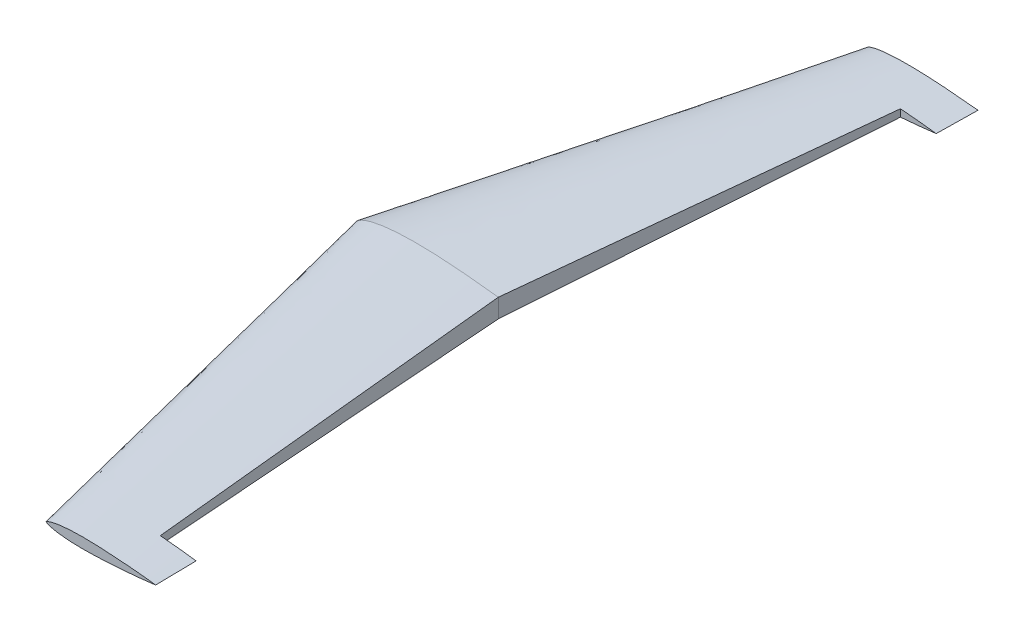
SolidWorks part; units mm, degrees
material "\"PLA\""
ref_plane "Front Plane" through (0, 0, 0) normal (0, 0, 1) x (1, 0, 0)
ref_plane "Top Plane" through (0, 0, 0) normal (0, 1, 0) x (1, 0, 0)
ref_plane "Right Plane" through (0, 0, 0) normal (1, 0, 0) x (0, 0, -1)
curve "NACA0015 top"
  spline degree 3 poles (1, 0, 0) (0.9834, 0.0035, 0) (0.9502, 0.0106, 0) (0.8834, 0.0206, 0) (0.8001, 0.0331, 0) (0.7001, 0.0461, 0) (0.6001, 0.0574, 0) (0.5001, 0.0666, 0) (0.4001, 0.0732, 0) (0.3167, 0.0755, 0) (0.25, 0.0746, 0) (0.1999, 0.0721, 0) (0.1498, 0.0673, 0) (0.108, 0.0607, 0) (0.0748, 0.0527, 0) (0.0493, 0.0448, 0) (0.0285, 0.0352, 0) (0.0083, 0.0224, 0) (0.0032, 0.0087, 0) (0, 0, 0) knots 0 0 0 0 0.049635 0.098913 0.19727 0.295402 0.393327 0.491044 0.588553 0.685896 0.734557 0.783276 0.832166 0.881486 0.906512 0.932076 0.958957 0.973952 1 1 1 1
curve "NACA0015 bottom"
  spline degree 3 poles (0, 0, 0) (0.0032, -0.0087, 0) (0.0083, -0.0224, 0) (0.0285, -0.0352, 0) (0.0493, -0.0448, 0) (0.0748, -0.0527, 0) (0.108, -0.0607, 0) (0.1498, -0.0673, 0) (0.1999, -0.0721, 0) (0.25, -0.0746, 0) (0.3167, -0.0755, 0) (0.4001, -0.0732, 0) (0.5001, -0.0666, 0) (0.6001, -0.0574, 0) (0.7001, -0.0461, 0) (0.8001, -0.0331, 0) (0.8834, -0.0206, 0) (0.9502, -0.0106, 0) (0.9834, -0.0035, 0) (1, 0, 0) knots 0 0 0 0 0.026048 0.041043 0.067924 0.093488 0.118514 0.167834 0.216724 0.265443 0.314104 0.411447 0.508956 0.606673 0.704598 0.80273 0.901087 0.950365 1 1 1 1
curve "NACA0012 top"
  spline degree 3 poles (1, 0, 0) (0.9999, 0.0005, 0) (0.9996, 0.0017, 0) (0.9971, 0.0015, 0) (0.9944, 0.0021, 0) (0.9903, 0.0026, 0) (0.9851, 0.0033, 0) (0.9787, 0.0042, 0) (0.9713, 0.0052, 0) (0.9627, 0.0064, 0) (0.9531, 0.0077, 0) (0.9424, 0.0091, 0) (0.9307, 0.0106, 0) (0.9179, 0.0122, 0) (0.9042, 0.014, 0) (0.8895, 0.0158, 0) (0.874, 0.0177, 0) (0.8575, 0.0196, 0) (0.8402, 0.0217, 0) (0.8222, 0.0237, 0) (0.8033, 0.0259, 0) (0.7838, 0.028, 0) (0.7636, 0.0302, 0) (0.7428, 0.0324, 0) (0.7214, 0.0345, 0) (0.6995, 0.0367, 0) (0.6772, 0.0388, 0) (0.6544, 0.0409, 0) (0.6313, 0.043, 0) (0.6078, 0.045, 0) (0.5841, 0.0469, 0) (0.5602, 0.0488, 0) (0.5362, 0.0505, 0) (0.5121, 0.0522, 0) (0.4879, 0.0537, 0) (0.4638, 0.0551, 0) (0.4398, 0.0563, 0) (0.4159, 0.0574, 0) (0.3922, 0.0583, 0) (0.3688, 0.0591, 0) (0.3456, 0.0596, 0) (0.3228, 0.0599, 0) (0.3005, 0.0601, 0) (0.2786, 0.06, 0) (0.2572, 0.0596, 0) (0.2364, 0.0591, 0) (0.2162, 0.0583, 0) (0.1966, 0.0572, 0) (0.1778, 0.056, 0) (0.1597, 0.0544, 0) (0.1425, 0.0527, 0) (0.126, 0.0507, 0) (0.1104, 0.0486, 0) (0.0958, 0.0462, 0) (0.0821, 0.0436, 0) (0.0693, 0.0408, 0) (0.0576, 0.0378, 0) (0.0468, 0.0347, 0) (0.0372, 0.0313, 0) (0.0286, 0.0279, 0) (0.0211, 0.0243, 0) (0.0147, 0.0206, 0) (0.0094, 0.0167, 0) (0.0053, 0.0128, 0) (0.0023, 0.0087, 0) (0.0004, 0.0044, 0) (0.0001, 0.0014, 0) (0, 0, 0) knots 0 0 0 0 0.001434 0.003166 0.006048 0.010073 0.015231 0.02151 0.028895 0.037368 0.046909 0.057494 0.069098 0.081695 0.095252 0.10974 0.125123 0.141363 0.158425 0.176266 0.194845 0.214118 0.234038 0.25456 0.275635 0.297214 0.319245 0.341677 0.364458 0.387533 0.410848 0.434349 0.457981 0.481687 0.505414 0.529104 0.552705 0.576159 0.599415 0.622418 0.645114 0.667453 0.689385 0.71086 0.731829 0.752247 0.77207 0.791254 0.809759 0.827545 0.844576 0.860818 0.876238 0.890807 0.904501 0.917294 0.929169 0.940111 0.950113 0.959173 0.967302 0.974522 0.980879 0.986449 0.991356 0.995786 1 1 1 1
sketch "Sketch3" plane through (0, 0, 0) normal (0, 0, 1) x (1, 0, 0)
  line L0 (0, 0) -> (1, 0) construction
  spline S0 degree 3 poles (0, 0) (0.0024, 0.0105) (0.0128, 0.0277) (0.0398, 0.0405) (0.0646, 0.05) (0.0904, 0.0566) (0.1157, 0.0618) (0.1436, 0.0662) (0.1764, 0.07) (0.2112, 0.0727) (0.2448, 0.0742) (0.2768, 0.075) (0.3075, 0.0751) (0.3387, 0.0747) (0.3674, 0.0739) (0.3979, 0.0727) (0.4325, 0.0709) (0.4699, 0.0685) (0.5072, 0.0656) (0.542, 0.0627) (0.5776, 0.0593) (0.6101, 0.056) (0.6429, 0.0525) (0.6719, 0.0492) (0.7011, 0.0457) (0.7283, 0.0423) (0.7621, 0.038) (0.7953, 0.0335) (0.8265, 0.029) (0.8531, 0.0251) (0.8826, 0.0207) (0.9141, 0.016) (0.9536, 0.0098) (0.9814, 0.004) (1, 0) knots 0 0 0 0 0.031271 0.055077 0.085653 0.108858 0.132715 0.161158 0.191102 0.229169 0.263044 0.289323 0.322456 0.35268 0.380449 0.406317 0.441553 0.481621 0.515849 0.550731 0.583502 0.620296 0.646048 0.679661 0.705503 0.732118 0.759389 0.805025 0.829931 0.851453 0.883388 0.917173 0.94435 1 1 1 1
  spline S5 degree 3 poles (1, 0) (0.9834, 0.0035) (0.9502, 0.0106) (0.8834, 0.0206) (0.8001, 0.0331) (0.7001, 0.0461) (0.6001, 0.0574) (0.5001, 0.0666) (0.4001, 0.0732) (0.3167, 0.0755) (0.25, 0.0746) (0.1999, 0.0721) (0.1498, 0.0673) (0.108, 0.0607) (0.0748, 0.0527) (0.0493, 0.0448) (0.0285, 0.0352) (0.0083, 0.0224) (0.0032, 0.0087) (0, 0) knots 0 0 0 0 0.049635 0.098913 0.19727 0.295402 0.393327 0.491044 0.588553 0.685896 0.734557 0.783276 0.832166 0.881486 0.906512 0.932076 0.958957 0.973952 1 1 1 1 construction
  spline S6 degree 3 poles (0, 0) (0.0026, -0.0103) (0.0124, -0.0274) (0.0352, -0.0382) (0.0549, -0.0467) (0.0763, -0.0531) (0.0989, -0.0585) (0.1215, -0.0628) (0.1441, -0.0662) (0.1678, -0.069) (0.1929, -0.0713) (0.2187, -0.073) (0.2432, -0.0741) (0.2682, -0.0748) (0.294, -0.0751) (0.3226, -0.075) (0.3496, -0.0744) (0.375, -0.0736) (0.3993, -0.0726) (0.4287, -0.0711) (0.4578, -0.0693) (0.4876, -0.0672) (0.5131, -0.0651) (0.5405, -0.0628) (0.5658, -0.0605) (0.5917, -0.0579) (0.6171, -0.0553) (0.6443, -0.0523) (0.6723, -0.0491) (0.6988, -0.046) (0.7231, -0.043) (0.7453, -0.0402) (0.768, -0.0372) (0.792, -0.0339) (0.8205, -0.0299) (0.8472, -0.026) (0.8731, -0.0221) (0.8949, -0.0189) (0.9178, -0.0154) (0.9394, -0.012) (0.9668, -0.0071) (0.9865, -0.0029) (1, 0) knots 0 0 0 0 0.031459 0.053378 0.072332 0.094059 0.118323 0.140338 0.161138 0.184859 0.210284 0.23444 0.260514 0.281647 0.30767 0.335622 0.365097 0.386713 0.409735 0.436157 0.472686 0.494853 0.5233 0.547147 0.575234 0.597407 0.623047 0.64982 0.677353 0.70536 0.727695 0.748701 0.770694 0.794596 0.819514 0.854489 0.873511 0.895859 0.918771 0.94123 0.959662 1 1 1 1
  spline S8 degree 3 poles (0, 0) (0, 0.0056) (0.0044, 0.0125) (0.012, 0.0188) (0.0216, 0.0249) (0.0334, 0.0301) (0.0509, 0.036) (0.0662, 0.0401) (0.084, 0.044) (0.0995, 0.0468) (0.1185, 0.0498) (0.1371, 0.0521) (0.1565, 0.0541) (0.1756, 0.0558) (0.1977, 0.0573) (0.2208, 0.0585) (0.2443, 0.0593) (0.2675, 0.0598) (0.2927, 0.0601) (0.3191, 0.06) (0.3457, 0.0596) (0.3715, 0.059) (0.3982, 0.0581) (0.4251, 0.057) (0.4546, 0.0556) (0.4861, 0.0538) (0.5172, 0.0519) (0.5479, 0.0497) (0.578, 0.0474) (0.6105, 0.0448) (0.6427, 0.042) (0.6728, 0.0393) (0.6998, 0.0367) (0.7284, 0.0338) (0.7575, 0.0308) (0.7894, 0.0274) (0.8221, 0.0238) (0.8573, 0.0197) (0.8931, 0.0154) (0.9405, 0.0093) (0.976, 0.0049) (1, 0) knots 0 0 0 0 0.015534 0.023148 0.028948 0.048951 0.06074 0.083424 0.095373 0.114484 0.12984 0.151868 0.169556 0.187127 0.208334 0.23486 0.255026 0.277502 0.303157 0.329099 0.355311 0.381272 0.40523 0.433818 0.460412 0.492192 0.526716 0.552057 0.582577 0.615545 0.647969 0.677813 0.704526 0.727746 0.762394 0.790552 0.82209 0.859297 0.894761 0.928143 1 1 1 1
  spline S10 degree 3 poles (0, 0) (0, -0.0056) (0.0044, -0.0125) (0.012, -0.0188) (0.0216, -0.0249) (0.0334, -0.0301) (0.0509, -0.036) (0.0662, -0.0401) (0.084, -0.044) (0.0995, -0.0468) (0.1185, -0.0498) (0.1371, -0.0521) (0.1565, -0.0541) (0.1756, -0.0558) (0.1977, -0.0573) (0.2208, -0.0585) (0.2443, -0.0593) (0.2675, -0.0598) (0.2927, -0.0601) (0.3191, -0.06) (0.3457, -0.0596) (0.3715, -0.059) (0.3982, -0.0581) (0.4251, -0.057) (0.4546, -0.0556) (0.4861, -0.0538) (0.5172, -0.0519) (0.5479, -0.0497) (0.578, -0.0474) (0.6105, -0.0448) (0.6427, -0.042) (0.6728, -0.0393) (0.6998, -0.0367) (0.7284, -0.0338) (0.7575, -0.0308) (0.7894, -0.0274) (0.8221, -0.0238) (0.8573, -0.0197) (0.8931, -0.0154) (0.9405, -0.0093) (0.976, -0.0049) (1, 0) knots 0 0 0 0 0.015534 0.023148 0.028948 0.048951 0.06074 0.083424 0.095373 0.114484 0.12984 0.151868 0.169556 0.187127 0.208334 0.23486 0.255026 0.277502 0.303157 0.329099 0.355311 0.381272 0.40523 0.433818 0.460412 0.492192 0.526716 0.552057 0.582577 0.615545 0.647969 0.677813 0.704526 0.727746 0.762394 0.790552 0.82209 0.859297 0.894761 0.928143 1 1 1 1
sketch "Sketch5" plane through (0, 0, 0) normal (0, 0, 1) x (1, 0, 0)
  spline S0 degree 3 poles (0, 0) (0.3574, 1.5678) (1.918, 4.1602) (5.9748, 6.0812) (9.6853, 7.4984) (13.5601, 8.4885) (17.359, 9.2744) (21.5371, 9.9268) (26.4618, 10.4957) (33.0301, 11.0042) (39.7779, 11.2375) (48.8818, 11.2764) (58.7619, 11.0016) (68.6835, 10.411) (82.6899, 9.3437) (94.1366, 8.1681) (108.8924, 6.4083) (116.551, 5.4163) (123.9756, 4.3543) (127.9601, 3.7705) (132.3938, 3.1058) (137.1154, 2.4024) (143.0353, 1.4683) (147.2037, 0.5967) (150, 0) knots 0 0 0 0 0.031271 0.055077 0.085653 0.108858 0.132715 0.161158 0.191102 0.229169 0.289323 0.322456 0.406317 0.481621 0.515849 0.679661 0.705503 0.805025 0.829931 0.851453 0.883388 0.917173 0.94435 1 1 1 1
  spline S1 degree 3 poles (0, 0) (0.3941, -1.5488) (1.8634, -4.1083) (5.2872, -5.7362) (8.2332, -6.9993) (11.4396, -7.9611) (14.8376, -8.7747) (18.2267, -9.4129) (21.6079, -9.924) (25.1774, -10.3516) (30.2639, -10.814) (36.5674, -11.1548) (45.6336, -11.3134) (54.66, -11.1386) (65.7291, -10.6179) (80.6284, -9.5535) (94.3915, -8.1361) (108.2354, -6.4878) (115.4814, -5.5561) (124.0381, -4.3507) (129.1858, -3.589) (134.2298, -2.8303) (137.6714, -2.3154) (140.9099, -1.8015) (145.0177, -1.0583) (147.9721, -0.4288) (150, 0) knots 0 0 0 0 0.031459 0.053378 0.072332 0.094059 0.118323 0.140338 0.161138 0.184859 0.210284 0.260514 0.30767 0.386713 0.436157 0.5233 0.677353 0.70536 0.794596 0.819514 0.873511 0.895859 0.918771 0.94123 0.959662 1 1 1 1
  dimension "D1" = 150
ref_plane "Plane1" through (0, 0, 300) normal (0, 0, 1) x (1, 0, 0)
sketch "Sketch6" plane through (0, 0, 300) normal (0, 0, 1) x (1, 0, 0)
  line L0 (75, 0) -> (155, 0) construction
  spline S2 degree 3 poles (75, 0) (75.1209, 0.0882) (75.7068, 0.4765) (77.2178, 1.1743) (79.4832, 1.8513) (82.264, 2.4461) (86.3979, 3.0879) (93.7425, 3.7284) (104.7997, 3.8884) (118.4044, 3.3774) (131.5746, 2.4566) (141.0004, 1.6037) (146.5064, 1.045) (150.2974, 0.635) (153.1157, 0.3346) (155, 0) knots 0.02353 0.02353 0.02353 0.02353 0.028948 0.048951 0.083424 0.114484 0.151868 0.23486 0.381272 0.552057 0.727746 0.859297 0.894761 0.928143 0.997377 0.997377 0.997377 0.997377
  spline S3 degree 3 poles (75, 0) (75.1209, -0.0882) (75.7068, -0.4765) (77.2178, -1.1743) (79.4832, -1.8513) (82.264, -2.4461) (86.3979, -3.0879) (93.7425, -3.7284) (104.7997, -3.8884) (118.4044, -3.3774) (131.5746, -2.4566) (141.0004, -1.6037) (146.5064, -1.045) (150.2974, -0.635) (153.1157, -0.3346) (155, 0) knots 0.02353 0.02353 0.02353 0.02353 0.028948 0.048951 0.083424 0.114484 0.151868 0.23486 0.381272 0.552057 0.727746 0.859297 0.894761 0.928143 0.997377 0.997377 0.997377 0.997377
  dimension "D1" = 80
  dimension "D2" = 75
ref_plane "Plane2" through (0, 0, -300) normal (0, 0, 1) x (1, 0, 0)
sketch "Sketch7" plane through (0, 0, -300) normal (0, 0, 1) x (1, 0, 0)
  line L0 (75, 0) -> (155, 0) construction
  spline S0 degree 3 poles (75, 0) (75.2065, 0.0964) (76.3351, 0.5814) (78.3681, 1.1995) (81.2775, 1.8363) (85.6038, 2.5291) (93.2928, 3.2364) (104.8724, 3.4591) (119.1234, 2.9916) (132.9213, 2.0929) (142.7974, 1.2465) (148.5667, 0.6889) (151.7123, 0.3638) (153.8382, 0.1465) (155, 0) knots 0.041089 0.041089 0.041089 0.041089 0.048951 0.083424 0.114484 0.151868 0.23486 0.381272 0.552057 0.727746 0.859297 0.894761 0.928143 0.968636 0.968636 0.968636 0.968636
  spline S1 degree 3 poles (75, 0) (75.2065, -0.0964) (76.3351, -0.5814) (78.3681, -1.1995) (81.2775, -1.8363) (85.6038, -2.5291) (93.2928, -3.2364) (104.8724, -3.4591) (119.1234, -2.9916) (132.9213, -2.0929) (142.7974, -1.2465) (148.5667, -0.6889) (151.7123, -0.3638) (153.8382, -0.1465) (155, 0) knots 0.041089 0.041089 0.041089 0.041089 0.048951 0.083424 0.114484 0.151868 0.23486 0.381272 0.552057 0.727746 0.859297 0.894761 0.928143 0.968636 0.968636 0.968636 0.968636
  spline S2 degree 3 poles (75, 0) (75.1209, 0.0882) (75.7068, 0.4765) (77.2178, 1.1743) (79.4832, 1.8513) (82.264, 2.4461) (86.3979, 3.0879) (93.7425, 3.7284) (104.7997, 3.8884) (118.4044, 3.3774) (131.5746, 2.4566) (141.0004, 1.6037) (146.5064, 1.045) (150.2974, 0.635) (153.1157, 0.3346) (155, 0) knots 0.02353 0.02353 0.02353 0.02353 0.028948 0.048951 0.083424 0.114484 0.151868 0.23486 0.381272 0.552057 0.727746 0.859297 0.894761 0.928143 0.997377 0.997377 0.997377 0.997377 construction
  dimension "D1" = 80
loft "Loft1" add profiles "Sketch7", "Sketch5" connector at (155, 0, -300) connector at (150, 0, 0)
loft "Loft2" add profiles "Sketch5<3>", "Sketch6"
sketch "Sketch5<3>" plane through (0, 0, 0) normal (0, 0, 1) x (1, 0, 0) same geometry as "Sketch5"
sketch "Sketch10" plane through (0, 0, 0) normal (0, 1, 0) x (1, 0, 0)
  line L0 (150, 0) -> (155, -300) construction
  line L1 (155, -300) -> (75, -300) construction
  line L2 (75, -300) -> (0, 0) construction
  line L3 (0, 0) -> (75, 300) construction
  line L4 (-12.4102, 300) -> (12.4102, 300) construction
  line L5 (155, 300) -> (75, 300) construction
  line L6 (75, 300) -> (155, 300) construction
  line L7 (150, 0) -> (155, 300) construction
  line L8 (155, 300) -> (150, 0) construction
  line L9 (150, 0) -> (0, 0) construction
  line L10 (150, 0) -> (105, 0) construction
  line L11 (155, 300) -> (131, 300) construction
  line L12 (155, -300) -> (131, -300) construction
  line L13 (131, -300) -> (105, 0) construction
  line L14 (105, 0) -> (131, 300) construction
  line L15 (154.5, 270) -> (128.4, 270)
  line L17 (128.4, -270) -> (154.5, -270)
  line L18 (154.5, -270) -> (150, 0)
  line L19 (150, 0) -> (154.5, 270)
  line L20 (128.4, 270) -> (105, 0)
  line L21 (105, 0) -> (128.4, -270)
  dimension "D1" = 45
  dimension "D2" = 24
  dimension "D3" = 30
  dimension "D4" = 30
  dimension "D5" = 24
extrude "Cut-Extrude1" cut sketch "Sketch10" against normal through all and the other way through all
